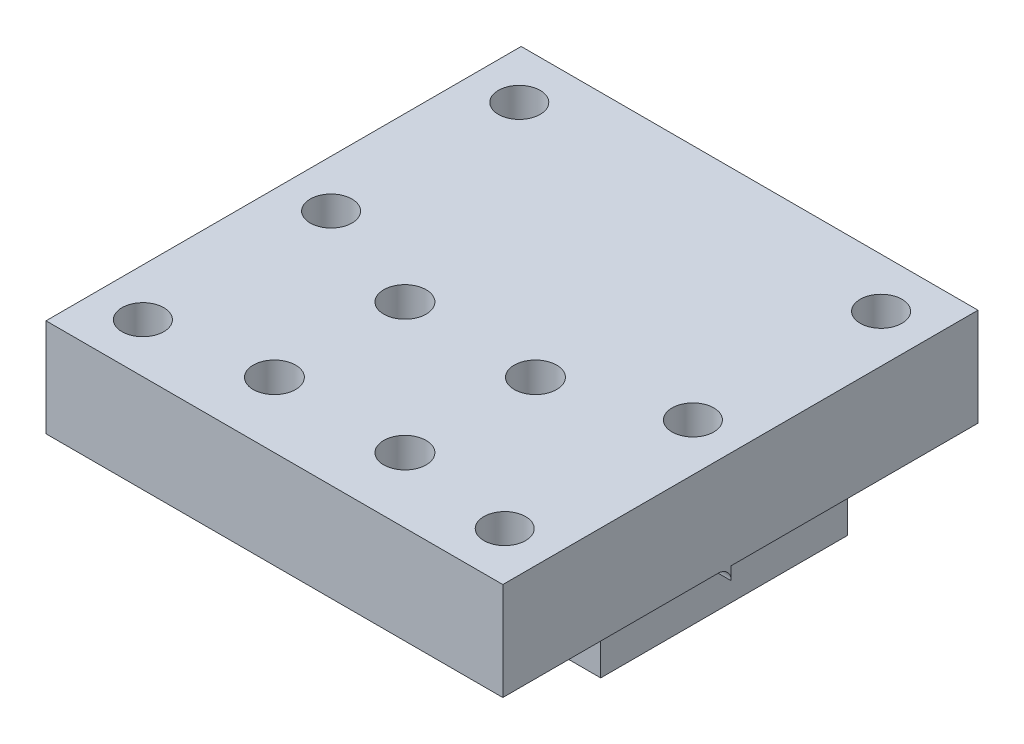
SolidWorks part; units mm, degrees
ref_plane "Front Plane" through (0, 0, 0) normal (0, 0, 1) x (1, 0, 0)
ref_plane "Top Plane" through (0, 0, 0) normal (0, 1, 0) x (1, 0, 0)
ref_plane "Right Plane" through (0, 0, 0) normal (1, 0, 0) x (0, 0, -1)
sketch "Sketch1" plane through (0, 0, 0) normal (0, 1, 0) x (1, 0, 0)
  line L1 (-35, 20) -> (35, 20)
  line L2 (-35, 20) -> (-35, -20)
  line L3 (-35, -20) -> (35, -20)
  line L4 (35, 20) -> (35, -20)
  line L5 (-35, 20) -> (35, -20) construction
  line L6 (-35, -20) -> (35, 20) construction
  line L7 (-10, 10) -> (10, 10) construction
  line L8 (-10, 10) -> (-10, -10) construction
  line L9 (-10, -10) -> (10, -10) construction
  line L10 (10, 10) -> (10, -10) construction
  line L11 (-10, 10) -> (10, -10) construction
  line L12 (-10, -10) -> (10, 10) construction
  circle A0 centre (10, 10) radius 1.6
  circle A1 centre (10, -10) radius 1.6
  circle A2 centre (-10, -10) radius 1.6
  circle A3 centre (-10, 10) radius 1.6
  point P0 (0, 0)
  point P5 (0, 0)
  point P21 (0, 0)
  dimension "D3" = 3.2
  dimension "D1" = 20
  dimension "D2" = 20
  dimension "D5" = 70
  dimension "D6" = 40
  dimension "D4" = 4
extrude "Boss-Extrude1" add sketch "Sketch1" along normal blind 15
sketch "Sketch2" plane through (0, 15, 0) normal (0, 1, 0) x (1, 0, 0)
  circle A0 centre (10, 10) radius 3.25
  circle A1 centre (10, -10) radius 3.25
  circle A2 centre (-10, -10) radius 3.25
  circle A3 centre (-10, 10) radius 3.25
  point P12 (0, 0)
  dimension "D1" = 6.5
  dimension "D2" = 4
extrude "Cut-Extrude1" cut sketch "Sketch2" against normal offset from surface (5 mm away) 10 up to face at (0, 0, 0)
sketch "Sketch3" plane through (0, 15, 0) normal (0, 1, 0) x (1, 0, 0)
  line L0 (35, 20) -> (-35, 20) construction
  line L5 (-35, 15) -> (35, 15)
  line L6 (-35, 15) -> (-35, 52.813)
  line L7 (-35, 52.813) -> (35, 52.813)
  line L8 (35, 15) -> (35, 52.813)
  line L9 (35, -20) -> (35, 20) construction
  line L10 (-35, 20) -> (-35, -20) construction
  dimension "D1" = 37.813
  dimension "D2" = 5
extrude "Boss-Extrude2" add sketch "Sketch3" against normal blind 39.8969
fillet "Fillet1" radius 2 1 edges at (0, 0, -15)
sketch "Sketch4" plane through (0, 15, 0) normal (0, 1, 0) x (1, 0, 0)
  line L0 (-35, 52.813) -> (35, -20) construction
  line L1 (-35, -20) -> (35, -20) construction
  line L2 (35, -20) -> (35, 52.813) construction
  line L3 (-35, -20) -> (35, 52.813) construction
  line L4 (0, 16.4065) -> (0, 35.737) construction
  line L5 (0, 16.4065) -> (23.279, 16.4065) construction
  line L6 (27.7218, 45.2423) -> (27.7218, -12.4293) construction
  circle A0 centre (27.7218, 45.2423) radius 3.2
  circle A1 centre (-27.7218, 45.2423) radius 3.2
  circle A2 centre (-27.7218, -12.4293) radius 3.2
  circle A3 centre (27.7218, -12.4293) radius 3.2
  circle A4 centre (27.7218, 16.4065) radius 3.2
  circle A5 centre (-27.7218, 16.4065) radius 3.2
  point P14 (0, 16.4065)
  dimension "D1" = 6.4
  dimension "D2" = 40
extrude "Cut-Extrude2" cut sketch "Sketch4" against normal blind 8
sketch "Sketch5" plane through (0, -24.8969, 0) normal (0, -1, 0) x (1, 0, 0)
  line L0 (-35, -52.813) -> (-35, -15) construction
  line L1 (-35, -30.9065) -> (35, -30.9065) construction
  line L2 (-35, -30.9065) -> (-35, -36.9065) construction
  line L3 (-35, -36.9065) -> (35, -36.9065) construction
  line L4 (35, -30.9065) -> (35, -36.9065) construction
  line L5 (35, -15) -> (35, -52.813) construction
  line L6 (-35, -33.9065) -> (35, -33.9065) construction
  line L7 (0, -22.9065) -> (0, -44.9065) construction
  circle A0 centre (0, -22.9065) radius 3.2
  circle A1 centre (0, -44.9065) radius 3.2
  circle A2 centre (-22, -22.9065) radius 3.2
  circle A3 centre (-22, -44.9065) radius 3.2
  point P10 (35, -33.9065)
  point P11 (0, -33.9065)
  dimension "D2" = 8
  dimension "D3" = 6.4
  dimension "D5" = 22
  dimension "D1" = 6
  dimension "D4" = 11
extrude "Cut-Extrude3" cut sketch "Sketch5" against normal blind 10
sketch "Sketch7" plane through (0, -24.8969, 0) normal (0, -1, 0) x (1, 0, 0)
  line L0 (35, -52.813) -> (-35, -52.813) construction
  line L1 (35, -15) -> (15, -15)
  line L2 (35, -15) -> (35, -52.813)
  line L3 (35, -52.813) -> (15, -52.813)
  line L4 (15, -15) -> (15, -52.813)
  dimension "D1" = 20
extrude "Cut-Extrude4" cut sketch "Sketch7" against normal up to surface (24.8969 mm away) up to face at (0, 0, 3.5)
fillet "Fillet2" radius 2 1 edges at (15, 0, -33.9065)
